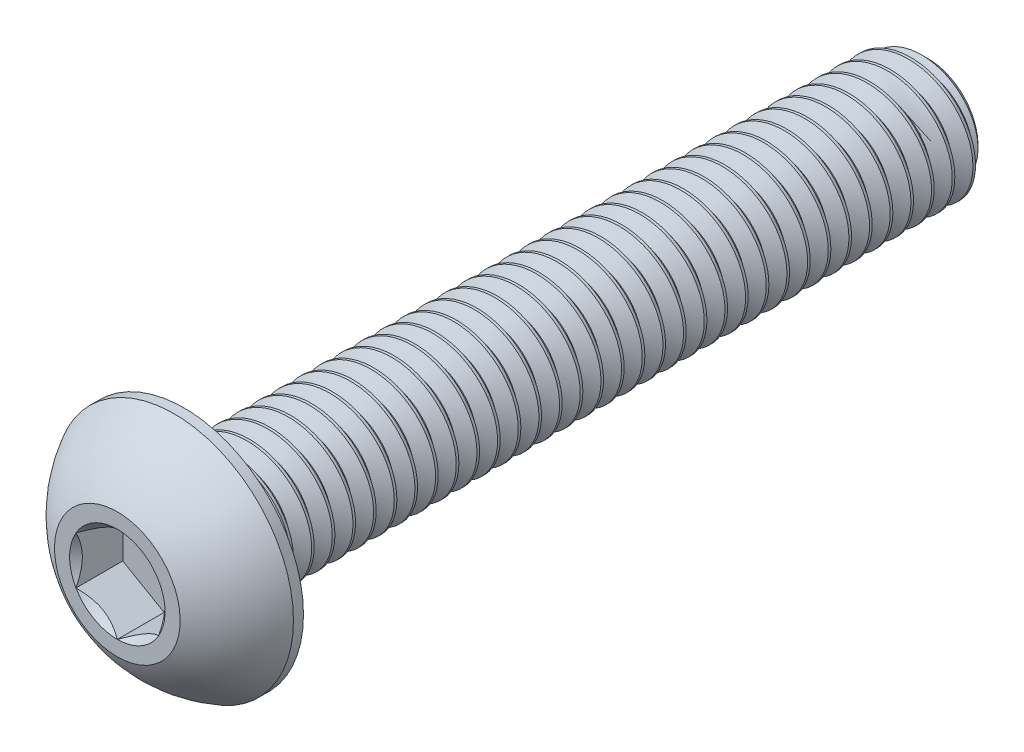
SolidWorks part; units mm, degrees
note: '?' marks a value the reader was unsure of.
material "Alloy Steel"
ref_plane "Front" through (0, 0, 0) normal (0, 0, 1) x (1, 0, 0)
ref_plane "Top" through (0, 0, 0) normal (0, 1, 0) x (1, 0, 0)
ref_plane "Right" through (0, 0, 0) normal (1, 0, 0) x (0, 0, -1)
sketch "Sketch1" plane through (0, 0, 0) normal (1, 0, 0) x (0, 0, -1)
  line L2 (2.5654, 2.413) -> (31.1404, 2.413) construction
  line L3 (31.1404, 2.413) -> (31.1404, 0) construction
  line L4 (31.1404, 0) -> (2.5654, 0) construction
  line L6 (2.1806, 4.5847) -> (2.5654, 4.5847) construction
  line L7 (31.1404, 2.413) -> (31.1404, -2.413) construction
  line L8 (0, 0) -> (2.5654, 0) construction
  line L9 (2.5654, 4.5847) -> (2.5654, -4.5847) construction
  line L11 (2.5654, 2.413) -> (2.5654, 0) construction
  line L13 (0, 1.5875) -> (0, -1.5875) construction
  line L14 (0, 1.5875) -> (0, 2.413) construction
  arc A3 (0, 2.413) -> (2.1806, 4.5847) centre (4.5749, 0) cw construction
  point P10 (29.9498, -2.413)
  point P16 (9.7091, 0)
  point P19 (23.9966, 0)
  dimension "D1" = 0.3848
  dimension "D2" = 1.1906
  dimension "D3" = 7.1437
  dimension "D4" = 7.1437
sketch "Sketch11" plane through (0, 0, 0) normal (1, 0, 0) x (0, 0, -1)
  line L1 (2.5654, 0) -> (31.1404, 0)
  line L4 (2.5654, 2.413) -> (31.1404, 2.413) construction
  line L5 (31.1404, 2.413) -> (31.1404, 0) construction
  line L8 (2.5654, 2.413) -> (31.1404, 2.413)
  line L9 (31.1404, 2.413) -> (31.1404, 0)
  line L10 (2.5654, 2.413) -> (2.5654, 0)
revolve "Revolve1" add sketch "Sketch11" angle 360 about L1
chamfer "Chamfer1" distance 0.4961 angle 45 1 edges at (0, -2.413, -31.1404)
sketch "Sketch7" plane through (0, 0, 0) normal (1, 0, 0) x (0, 0, -1)
  line L6 (2.1806, 4.5847) -> (2.5654, 4.5847) construction
  line L8 (0, 0) -> (2.5654, 0) construction
  line L11 (2.5654, 4.5847) -> (2.5654, -4.5847) construction
  line L12 (2.1806, 4.5847) -> (2.5654, 4.5847)
  line L13 (0, 0) -> (2.5654, 0)
  line L14 (0, 1.5875) -> (0, -1.5875) construction
  line L15 (2.5654, 4.5847) -> (2.5654, 0)
  line L16 (0, 2.413) -> (0, 0)
  arc A2 (2.1806, 4.5847) -> (0, 2.413) centre (4.5749, 0) ccw construction
  arc A3 (2.1806, 4.5847) -> (0, 2.413) centre (4.5749, 0) ccw
revolve "Revolve2" add sketch "Sketch7" angle 360 mid plane about L13
sketch "Sketch5" plane through (0, 0, 0) normal (0, 0, 1) x (1, 0, 0)
  line L1 (1.5875, -0.9165) -> (1.5875, 0.9165)
  line L2 (1.5875, 0.9165) -> (0, 1.8331)
  line L3 (0, 1.8331) -> (-1.5875, 0.9165)
  line L4 (-1.5875, 0.9165) -> (-1.5875, -0.9165)
  line L5 (-1.5875, -0.9165) -> (0, -1.8331)
  line L6 (0, -1.8331) -> (1.5875, -0.9165)
  circle A0 centre (0, 0) radius 1.5875 construction
extrude "Cut-Extrude2" cut sketch "Sketch5" against normal blind 1.7958
sketch "Sketch6" plane through (0, 0, 0) normal (0, 0, 1) x (1, 0, 0)
  circle A0 centre (0, 0) radius 1.8331
extrude "Cut-Extrude3" cut sketch "Sketch6" against normal blind 1.7958 draft 45
sketch "Sketch3" plane through (0, 0, -31.1404) normal (0, 0, -1) x (-1, 0, 0)
  circle A0 centre (0, 0) radius 2.413
curve "Helix/Spiral1" pitch 0.7937 height 29.3687 turns 37
sketch "Sketch2" plane through (0, 0, 0) normal (1, 0, 0) x (0, 0, -1)
  line L0 (31.0908, 2.4989) -> (31.8845, 2.4989) construction
  line L1 (31.8845, 2.4989) -> (31.4877, 1.8115) construction
  line L2 (31.4877, 1.8115) -> (31.0908, 2.4989) construction
  line L3 (31.4877, 1.8115) -> (31.4877, 1.8974) construction
  line L4 (31.4877, 1.8974) -> (31.4877, 2.413) construction
  line L5 (31.4877, 2.413) -> (31.4877, 2.4989) construction
  line L6 (31.5373, 1.8974) -> (31.4381, 1.8974) construction
  line L7 (31.8349, 2.413) -> (31.1404, 2.413) construction
  line L8 (31.8597, 2.456) -> (31.1156, 2.456) construction
  line L9 (31.1156, 2.456) -> (31.8597, 2.456)
  line L10 (31.8597, 2.456) -> (31.5373, 1.8974)
  line L11 (31.5373, 1.8974) -> (31.4381, 1.8974)
  line L12 (31.4381, 1.8974) -> (31.1156, 2.456)
  line L13 (31.1404, 2.413) -> (2.5654, 2.413) construction
  line L14 (31.1404, -2.413) -> (31.1404, 2.413)
  line L15 (31.1404, -2.413) -> (31.1404, 2.413) construction
  line L16 (2.5654, -4.5847) -> (2.5654, 4.5847) construction
  point P10 (31.4877, 1.8974)
  point P11 (31.4877, 2.413)
  point P16 (31.4877, 2.456)
  dimension "D1" = 0.7937
  dimension "D2" = 0.0992
sweep "Cut-Sweep1" cut profiles "Sketch2" path "Helix/Spiral1"
sketch "Sketch9" [suppressed] plane through (0, 0, -6.731) normal (0, 0, 1) x (1, 0, 0)
  circle A2 centre (0, 0) radius 6.35
extrude "Boss-Extrude2" [suppressed] add sketch "Sketch9" against normal offset from surface (57.15 mm away) 31.75
ref_axis "Center Axis 1" through (0, 0, -30.6443) along (0, 0, 1)?
ref_plane "Contact Plane 1" through (0, 0, -2.5654) normal (0, 0, -1) x (-1, 0, 0)
ref_plane "Contact Plane 2" through (0, 0, -31.1404) normal (0, 0, -1) x (-1, 0, 0)
equation "\"D3@Helix/Spiral1\" = \"Lg@Sketch1\" + \"D4@Helix/Spiral1\""
equation "\"D1@Chamfer1\"=\"D4@Helix/Spiral1\" * .625"
equation "\"D1@Cut-Extrude2\" = \"Head Ht@Sketch1\" * .7"
equation "\"D1@Sketch1\" = \"Head Ht@Sketch1\" * .15"
equation "\"D1@Cut-Extrude3\" = \"D1@Cut-Extrude2\""
equation "\"D2@Sketch1\"=\"D4@Helix/Spiral1\"*1.5"
equation "\"D3@Sketch1\"=\"Lg@Sketch1\"/4"
equation "\"D4@Sketch1\"=\"D3@Sketch1\""
equation "\"D1@Sketch2\"=\"D4@Helix/Spiral1\""
equation "\"D2@Sketch2\"=\"D1@Sketch2\"/8"
